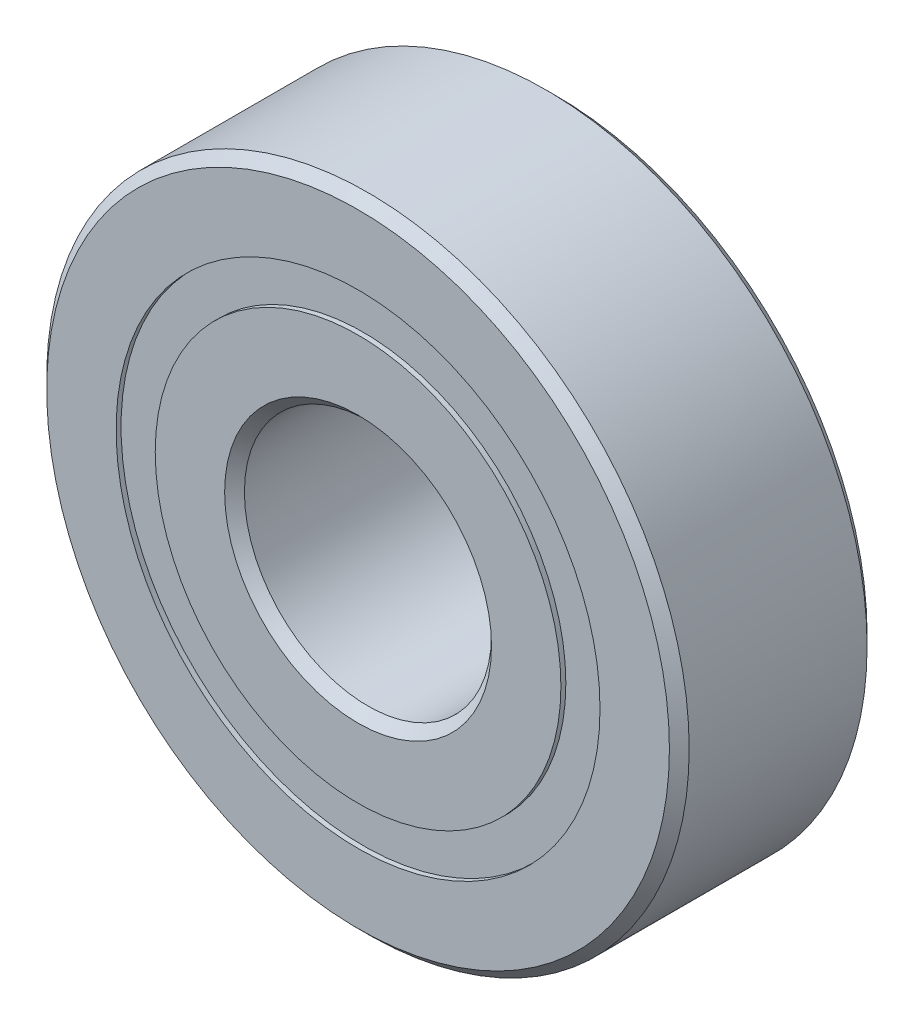
SolidWorks part; units mm, degrees
ref_plane "Front Plane" through (0, 0, 0) normal (0, 0, 1) x (1, 0, 0)
ref_plane "Top Plane" through (0, 0, 0) normal (0, 1, 0) x (1, 0, 0)
ref_plane "Right Plane" through (0, 0, 0) normal (1, 0, 0) x (0, 0, -1)
sketch "Sketch1" plane through (0, 0, 0) normal (1, 0, 0) x (0, 0, -1)
  line L0 (-2, 0) -> (2, 0) construction
  line L1 (0, 6.5) -> (0, -6.5) construction
  line L2 (1.8, 6.5) -> (-1.8, 6.5)
  line L3 (-1.8, 6.5) -> (-2, 6.3)
  line L4 (-2, 6.3) -> (-2, 4.8956)
  line L5 (-2, 4.8956) -> (-0.8889, 4.8956)
  line L6 (2, 4.8956) -> (0.8889, 4.8956)
  line L7 (2, 6.3) -> (2, 4.8956)
  line L8 (1.8, 6.5) -> (2, 6.3)
  line L9 (0, 6.5) -> (0, 4.5) construction
  line L10 (0, 4.5) -> (0, 2.5) construction
  arc A0 (-0.8889, 4.8956) -> (0.8889, 4.8956) centre (0, 4.5) cw
  point P14 (0, 2.5)
  dimension "D3" = 1.7778
  dimension "D1" = 45
  dimension "Width" = 4
  dimension "OD" = 13
  dimension "D2" = 0.2
  dimension "Shaft Dia" = 5
  dimension "D4" = 0.3956
revolve "Revolve1" add sketch "Sketch1" angle 360 about L0
sketch "Sketch3" plane through (0, 0, 0) normal (1, 0, 0) x (0, 0, -1)
  line L0 (-2, 4.1044) -> (-0.8889, 4.1044)
  line L1 (0, 6.5) -> (0, -6.5) construction
  line L2 (-2, 6.3) -> (-2, 4.8956) construction
  line L3 (-2, 4.1044) -> (-2, 2.7)
  line L4 (-1.8, 6.5) -> (-2, 6.3) construction
  line L5 (-2, 2.7) -> (-1.8, 2.5)
  line L6 (-1.8, 2.5) -> (1.8, 2.5)
  line L7 (1.8, 6.5) -> (1.8, -6.5) construction
  line L8 (1.8, 2.5) -> (2, 2.7)
  line L9 (2, -6.3) -> (2, 6.3) construction
  line L10 (2, 2.7) -> (2, 4.1044)
  line L11 (2, 4.1044) -> (0.8889, 4.1044)
  line L13 (1.8, 6.5) -> (2, 6.3) construction
  arc A0 (0.8889, 4.8956) -> (-0.8889, 4.8956) centre (0, 4.5) ccw construction
  arc A1 (0.8889, 4.1044) -> (-0.8889, 4.1044) centre (0, 4.5) cw
revolve "Revolve3" add sketch "Sketch3" angle 360 about L0
sketch "Sketch4" plane through (0, 0, 0) normal (1, 0, 0) x (0, 0, -1)
  line L0 (-0.9729, 4.5) -> (0.9729, 4.5)
  arc A2 (-0.9729, 4.5) -> (0.9729, 4.5) centre (0, 4.5) cw
  arc A3 (0.8889, 4.8956) -> (-0.8889, 4.8956) centre (0, 4.5) ccw construction
revolve "Revolve4" add sketch "Sketch4" angle 360 about L0
ref_axis "Axis1" through (0, 0, -2) along (0, 0, 1)
pattern_circular "CirPattern1" count 12 every 30 about axis through (0, 0, -2) along (0, 0, 1) of bodies 104
sketch "Sketch5" plane through (0, 0, 0) normal (1, 0, 0) x (0, 0, -1)
  line L0 (-2, 4.8956) -> (-0.8889, 4.8956) construction
  line L1 (-1.9, 4.8956) -> (-0.9729, 4.8956)
  line L2 (-1.9, 4.8956) -> (-1.9, 4.1044)
  line L3 (-1.9, 4.1044) -> (-0.9729, 4.1044)
  line L4 (-0.9729, 4.8956) -> (-0.9729, 4.1044)
  line L5 (-2, 4.1044) -> (-0.8889, 4.1044) construction
  line L6 (2, 4.8956) -> (0.8889, 4.8956) construction
  line L7 (1.9, 4.8956) -> (0.9729, 4.8956)
  line L8 (1.9, 4.8956) -> (1.9, 4.1044)
  line L9 (1.9, 4.1044) -> (0.9729, 4.1044)
  line L10 (0.9729, 4.8956) -> (0.9729, 4.1044)
  line L11 (2, 4.1044) -> (0.8889, 4.1044) construction
  line L12 (-1.8, 6.5) -> (-2, 6.3) construction
  point P18 (-1.9, 6.4)
revolve "Revolve5" add sketch "Sketch5" angle 360 about L0
sketch "Sketch6" plane through (0, 0, 0) normal (1, 0, 0) x (0, 0, -1)
  line L0 (2, 0) -> (-2, 0) construction
  line L1 (2, 4.8956) -> (1.2126, 4.8956)
  line L2 (2, 4.8956) -> (2, 6.9469)
  line L3 (2, 6.9469) -> (1.2126, 6.9469)
  line L4 (1.2126, 4.8956) -> (1.2126, 6.9469)
  dimension "Th" = 0.7874
  dimension "Flange OD" = 13.8938
revolve "Revolve6" [suppressed] add sketch "Sketch6" angle 360 about L0
equation "\"D2@Sketch1\" = \"Width@Sketch1\"*.05"
equation "\"D3@Sketch1\" = \"Width@Sketch1\"/2.25"
equation "\"D4@Sketch1\" = (((\"OD@Sketch1\"-\"Width@Sketch1\")/2)/3.25)/3.5"
equation "\"D2@CirPattern1\" = 360/\"Balls@CirPattern1\""
